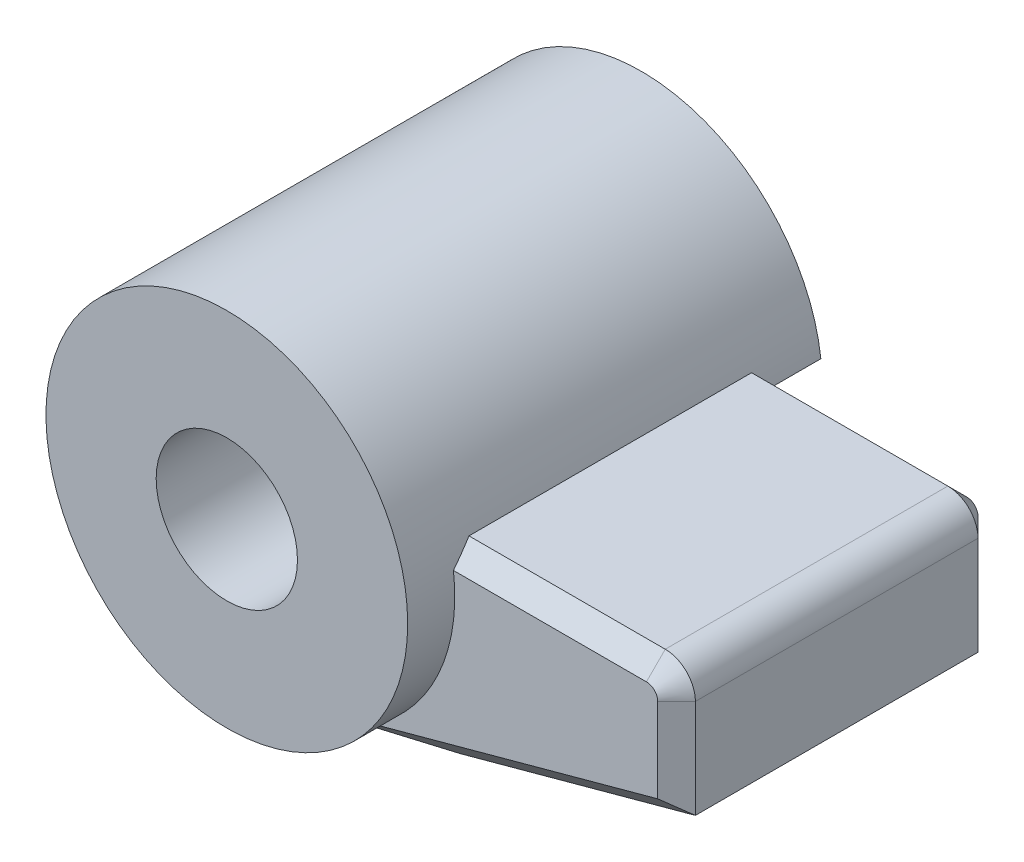
SolidWorks part; units mm, degrees
ref_plane "정면" through (0, 0, 0) normal (0, 0, 1) x (1, 0, 0)
ref_plane "윗면" through (0, 0, 0) normal (0, 1, 0) x (1, 0, 0)
ref_plane "우측면" through (0, 0, 0) normal (1, 0, 0) x (0, 0, -1)
sketch "스케치1" plane through (0, 0, 0) normal (0, 0, 1) x (1, 0, 0)
  line L0 (0, 0) -> (0, -4.8) construction
  line L1 (4.6763, 1.0828) -> (10.686, 1.0828)
  line L4 (10.686, 1.0828) -> (10.686, -2.3372)
  line L6 (2.0768, -4.3274) -> (4.4636, -4.0334)
  line L7 (4.4636, -4.0334) -> (10.686, -2.3372)
  circle A0 centre (0, 0) radius 4.8
  circle A1 centre (0, 0) radius 1.875
  dimension "D1" = 9.6
  dimension "D2" = 3.75
extrude "보스-돌출1" add sketch "스케치1" along normal mid plane 11 contours A0 A1 region at (4.6341, 0.5295, 0)
extrude "보스-돌출2" add sketch "스케치1<3>" along normal mid plane 8.5 contours A0 L4 L1 region at (7.1916, -1.2697, 0)
sketch "스케치1<3>" plane through (0, 0, 0) normal (0, 0, 1) x (1, 0, 0) same geometry as "스케치1"
sketch "스케치2" plane through (0, 0, 0) normal (0, 0, 1) x (1, 0, 0)
  line L0 (0, 0) -> (4.0346, 0.353) construction
  line L1 (3.486, 2.0617) -> (2.336, 1.9611)
  line L2 (3.791, -1.425) -> (2.641, -1.5256)
  line L3 (0, 0) -> (5, 0) construction
  circle A0 centre (0, 0) radius 1.925
  arc A1 (2.336, 1.9611) -> (2.641, -1.5256) centre (0, 0) ccw
  arc A2 (3.791, -1.425) -> (3.486, 2.0617) centre (0, 0) ccw
  dimension "D1" = 6.1
  dimension "D2" = 8.1
  dimension "D3" = 3.5
  dimension "D4" = 3.85
  dimension "D5" = 5
extrude "컷-돌출1" [suppressed] cut sketch "스케치2" against normal through all
fillet "필렛1" radius 0.8 1 edges at (10.686, 1.0828, 0)
chamfer "모따기1" distance 0.5 angle 45 8 edges at (7.5748, -3.1853, 4.25) (7.5748, -3.1853, -4.25) (7.2811, 1.0828, 4.25) (10.4517, 0.8485, 4.25) (10.686, -1.0272, 4.25) (7.2811, 1.0828, -4.25) (10.4517, 0.8485, -4.25) (10.686, -1.0272, -4.25)
sketch "스케치3" plane through (0, 0, -5.5) normal (0, 0, -1) x (-1, 0, 0)
  circle A0 centre (0, 0) radius 4
  dimension "D1" = 8
extrude "컷-돌출2" cut sketch "스케치3" against normal blind 7
sketch "스케치4" plane through (0, 0, -5.5) normal (0, 0, -1) x (-1, 0, 0)
  line L0 (0, 0) -> (-6.8632, -1.3772) construction
  line L1 (-6.8632, -1.3772) -> (-7.1583, 0.0935)
  line L2 (-7.1583, 0.0935) -> (-3.6288, 0.8017)
  line L3 (-3.6288, 0.8017) -> (-3.3337, -0.6689)
  line L4 (-3.0385, -2.1396) -> (-3.3337, -0.6689)
  line L5 (-6.5681, -2.8479) -> (-3.0385, -2.1396)
  line L6 (-6.8632, -1.3772) -> (-6.5681, -2.8479)
  dimension "D1" = 90
  dimension "D2" = 7
  dimension "D3" = 3
extrude "컷-돌출3" cut sketch "스케치4" against normal blind 6
